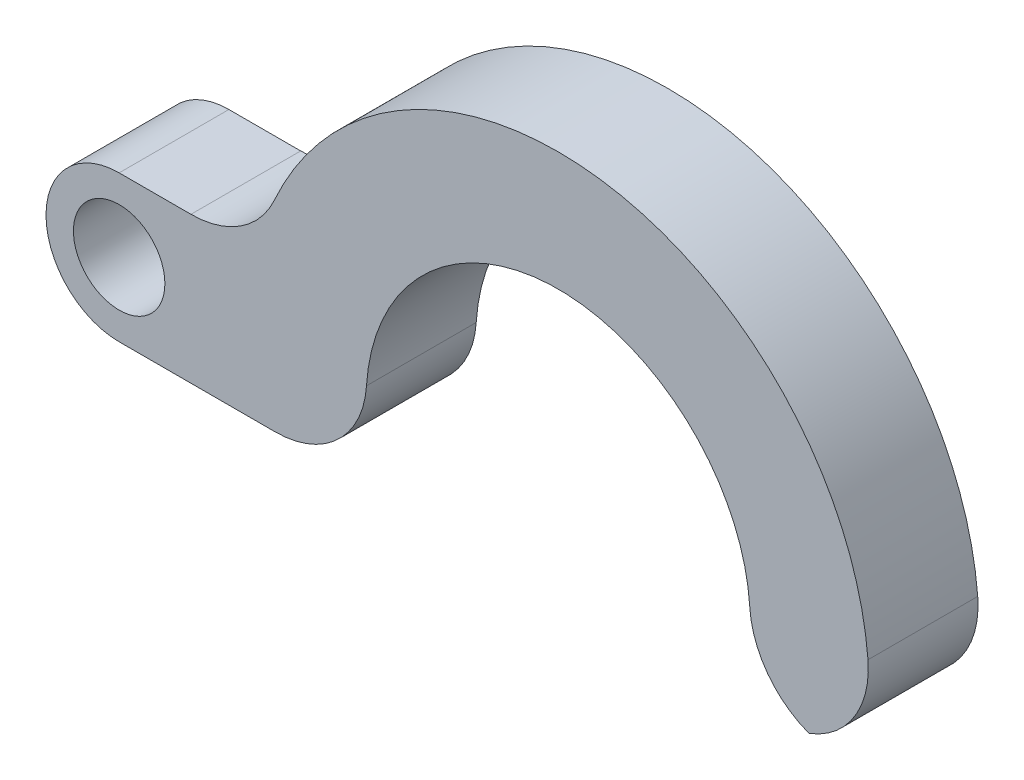
SolidWorks part; units mm, degrees
ref_plane "Спереди" through (0, 0, 0) normal (0, 0, 1) x (1, 0, 0)
ref_plane "Сверху" through (0, 0, 0) normal (0, 1, 0) x (1, 0, 0)
ref_plane "Справа" through (0, 0, 0) normal (1, 0, 0) x (0, 0, -1)
other "Configuration Table"
sketch "Эскиз1" plane through (0, 0, 0) normal (0, 0, 1) x (1, 0, 0)
  line L0 (18.3557, 0) -> (-17.7727, 0) construction
  line L1 (-8.2614, 2) -> (-12, 2)
  line L2 (-12, 2) -> (-12, 0)
  line L3 (-12, -2) -> (-8.2614, -2)
  line L4 (-12, 0) -> (-12, -2)
  line L5 (-8.2614, -2) -> (-4.8541, -2)
  line L6 (-4.8541, -2) -> (4.8541, -2) construction
  line L7 (4.8541, -2) -> (8.2614, -2)
  circle A0 centre (0, 0) radius 5.25
  circle A1 centre (0, 0) radius 8.5
  circle A2 centre (-12, 0) radius 2
  circle A3 centre (-12, 0) radius 1.25
  point P8 (-12, 0)
  dimension "D1" = 10.5
  dimension "D2" = 17
  dimension "D5" = 2.5
  dimension "D3" = 4
  dimension "D4" = 12
extrude "Бобышка-Вытянуть1" add sketch "Эскиз1" along normal blind 3 contours A1 L5 A0 L7 | A2 L3 A1 L1 | L4 A2 L2 | L2 A2 L4 region at (-9.4734, 0, 0) region at (0.9834, 8.2417, 0) region at (-10.6174, 1.3826, 0) region at (-12.0447, 1.625, 0)
fillet "Скругление2" radius 2.5 4 edges at (-4.8541, -2, 1.5) (-8.2614, 2, 1.5) (8.2614, -2, 1.5) (4.8541, -2, 1.5)
